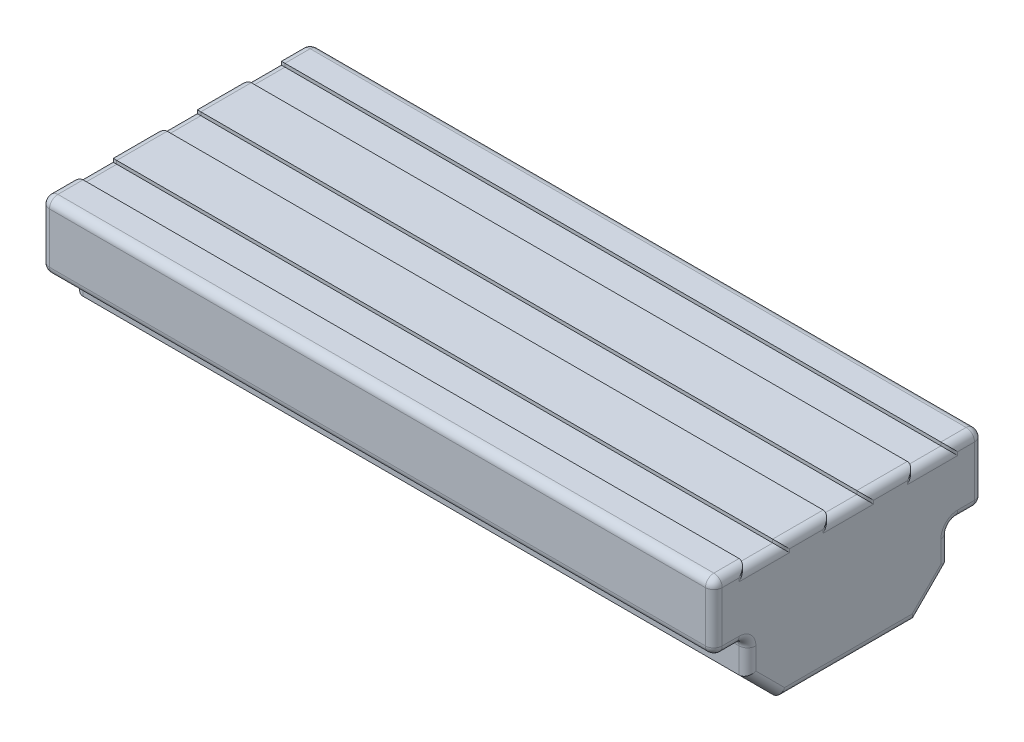
SolidWorks part; units mm, degrees
note: '?' marks a value the reader was unsure of.
ref_plane "Front Plane" through (0, 0, 0) normal (0, 0, 1) x (1, 0, 0)
ref_plane "Top Plane" through (0, 0, 0) normal (0, 1, 0) x (1, 0, 0)
ref_plane "Right Plane" through (0, 0, 0) normal (1, 0, 0) x (0, 0, -1)
sketch "Esquisse1" plane through (0, 0, 0) normal (0, 1, 0) x (1, 0, 0)
  line L1 (-20, 4) -> (20, 4)
  line L2 (-20, 4) -> (-20, -4)
  line L3 (-20, -4) -> (20, -4)
  line L4 (20, 4) -> (20, -4)
  line L5 (-20, 4) -> (20, -4) construction
  line L6 (-20, -4) -> (20, 4) construction
  point P0 (0, 0)
  dimension "D1" = 40
  dimension "D2" = 8
extrude "Boss.-Extru.1" add sketch "Esquisse1" along normal blind 8
sketch "Esquisse5" plane through (-20, 0, 0) normal (-1, 0, 0) x (0, 0, 1)
  line L0 (-4, 0) -> (-6, 2)
  line L1 (-6, 2) -> (-6, 8)
  line L2 (-6, 8) -> (-4, 8)
  line L3 (-4, 8) -> (-4, 0) construction
  line L4 (-4, 8) -> (-4, 0)
  dimension "D1" = 2
  dimension "D2" = 45
other "AlignerGroupe1" parameters "D1"=2.4483, "D2"=0
ref_axis "Axe1" through (-20, 8, 0) along (0, -1, 0)?
ref_plane "Plan1" through (0, 0, 0) normal (0, 0, -1) x (0, -1, 0)
extrude "Boss.-Extru.3" add sketch "Esquisse5" against normal blind 40
mirror "Symétrie2" about plane through (0, 0, 0) normal (0, 0, -1) of "Boss.-Extru.3"
sketch "Esquisse6" plane through (0, 0, -6) normal (0, 0, -1) x (-1, 0, 0)
  line L0 (20, 8) -> (20, 2) construction
  line L1 (-20, 8) -> (20, 8)
  line L2 (-20, 8) -> (-20, 4)
  line L3 (-20, 4) -> (20, 4)
  line L4 (20, 8) -> (20, 4)
  dimension "D1" = 4
extrude "Boss.-Extru.4" add sketch "Esquisse6" along normal blind 2
mirror "Symétrie4" about plane through (0, 0, 0) normal (0, 0, -1) of "Boss.-Extru.4"
ref_plane "Plan2" through (0, 0, 0) normal (1, 0, 0) x (0, 0, -1)
sketch "Esquisse7" plane through (0, 0, 0) normal (0, -1, 0) x (1, 0, 0)
  circle A0 centre (-15, 0) radius 2
  dimension "D1" = 4
extrude "Enlèv. mat.-Extru.1" cut sketch "Esquisse7" against normal blind 6
mirror "Symétrie10" about plane through (0, 0, 0) normal (1, 0, 0) of "Enlèv. mat.-Extru.1"
sketch "Esquisse10" plane through (0, 8, 0) normal (0, 1, 0) x (1, 0, 0)
  line L0 (-20, 8) -> (-20, -8) construction
  line L1 (-20, 1) -> (20, 1)
  line L2 (-20, 1) -> (-20, -1)
  line L3 (-20, -1) -> (20, -1)
  line L4 (20, 1) -> (20, -1)
  line L5 (20, -8) -> (20, 8) construction
  line L6 (4.4, 0) -> (-4.4, 0) construction
  line L7 (-20, 6) -> (20, 6)
  line L8 (-20, 6) -> (-20, 4)
  line L9 (-20, 4) -> (20, 4)
  line L10 (20, 6) -> (20, 4)
  line L11 (-20, -4) -> (20, -4)
  line L12 (-20, -4) -> (-20, -6)
  line L13 (-20, -6) -> (20, -6)
  line L14 (20, -4) -> (20, -6)
  dimension "D1" = 2
  dimension "D2" = 2
  dimension "D3" = 2
  dimension "D4" = 1
  dimension "D5" = 4
  dimension "D6" = 4
extrude "Enlèv. mat.-Extru.4" cut sketch "Esquisse10" against normal blind 0.2
fillet "Congé2" radius 0.5 2 edges at (0, 8, 8) (0, 8, -8)
fillet "Congé3" radius 0.5 4 edges at (0, 4, 6) (0, 4, 8) (0, 4, -8) (0, 4, -6)
fillet "Congé4" radius 0.5 52 edges at (20, 7.8536, 7.8536) (20, 8, 6.75) (20, 7.9, 6) (20, 7.8, 5) (20, 7.9, 4) (20, 8, -2.5) (20, 7.9, 1) (20, 7.8, 0) (20, 7.9, -1) (20, 7.9, -4) (20, 7.8, -5) (20, 7.9, -6) (20, 7.8536, -7.8536) (20, 6, -8) (20, 4.1464, -7.8536) (20, 4, -7) (20, 3.8536, -6.1464) (-20, 2.75, -6) (20, 2.75, -6) (-20, 1, -5) (20, 1, -5) (20, 0, 0) (-20, 1, 5) (20, 1, 5) (20, 2.75, 6) (-20, 2.75, 6) (20, 3.8536, 6.1464) (-20, 4, 7) (20, 4, 7) (20, 4.1464, 7.8536) (-20, 6, 8) (20, 6, 8) (-20, 3.8536, 6.1464) (-20, 0, 0) (-20, 3.8536, -6.1464) (-20, 4, -7) (-20, 4.1464, -7.8536) (-20, 6, -8) (-20, 7.8536, -7.8536) (-20, 8, 6.75) (-20, 8, -2.5) (-20, 7.9, -6) (-20, 7.8, -5) (-20, 7.9, -4) (-20, 7.9, -1) (-20, 7.8, 0) (-20, 7.9, 1) (-20, 7.9, 4) (-20, 7.8, 5) (-20, 7.9, 6) (-20, 7.8536, 7.8536) (-20, 4.1464, 7.8536)
